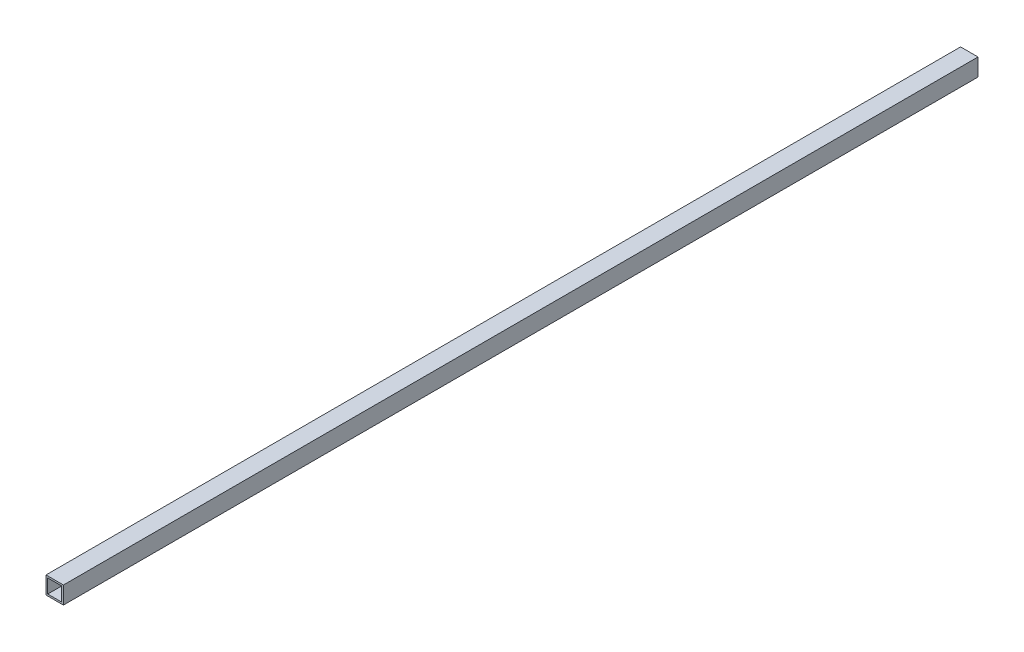
SolidWorks part; units mm, degrees
ref_plane "Front Plane" through (0, 0, 0) normal (0, 0, 1) x (1, 0, 0)
ref_plane "Top Plane" through (0, 0, 0) normal (0, 1, 0) x (1, 0, 0)
ref_plane "Right Plane" through (0, 0, 0) normal (1, 0, 0) x (0, 0, -1)
sketch "Sketch1" plane through (0, 0, 0) normal (0, 0, 1) x (1, 0, 0)
  line L1 (0, 0) -> (19.05, 0)
  line L2 (0, 0) -> (0, 19.05)
  line L3 (0, 19.05) -> (19.05, 19.05)
  line L4 (19.05, 0) -> (19.05, 19.05)
  dimension "D1" = 19.05
  dimension "D2" = 19.05
extrude "Boss-Extrude1" add sketch "Sketch1" against normal blind 1000.125
sketch "Sketch2" plane through (0, 0, 0) normal (0, 0, 1) x (1, 0, 0)
  line L0 (19.05, 0) -> (19.05, 19.05) construction
  line L1 (1.905, 17.145) -> (17.145, 17.145)
  line L2 (1.905, 17.145) -> (1.905, 1.905)
  line L3 (1.905, 1.905) -> (17.145, 1.905)
  line L4 (17.145, 17.145) -> (17.145, 1.905)
  line L5 (19.05, 19.05) -> (0, 19.05) construction
  line L6 (0, 0) -> (19.05, 0) construction
  dimension "D1" = 15.24
  dimension "D2" = 15.24
  dimension "D3" = 1.905
  dimension "D4" = 1.905
  dimension "D5" = 1.905
extrude "Cut-Extrude1" cut sketch "Sketch2" against normal through all
